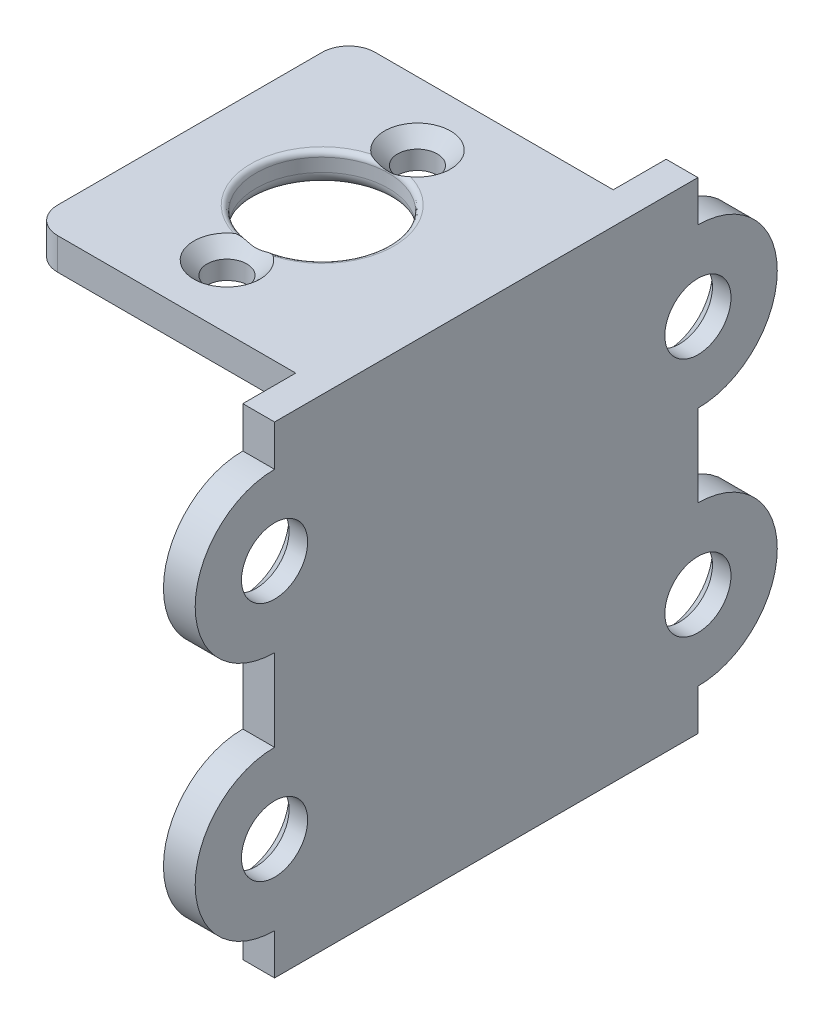
SolidWorks part; units mm, degrees
ref_plane "Front" through (0, 0, 0) normal (0, 0, 1) x (1, 0, 0)
ref_plane "Top" through (0, 0, 0) normal (0, 1, 0) x (1, 0, 0)
ref_plane "Right" through (0, 0, 0) normal (1, 0, 0) x (0, 0, -1)
sketch "Sketch1" plane through (0, 0, 0) normal (0, 1, 0) x (1, 0, 0)
  line L9 (0, 6) -> (5, 6)
  line L11 (-5, -6) -> (5, -6)
  line L12 (-5, -6) -> (-5, 6)
  line L13 (-5, 6) -> (5, 6)
  line L14 (5, -6) -> (5, 6)
  circle A3 centre (0, 0) radius 2.5
  circle A4 centre (0, 3.6) radius 0.75
  circle A5 centre (0, -3.6) radius 0.75
extrude "Boss-Extrude3" add sketch "Sketch1" along normal blind 1.2 contours L11 L14 L9 L13 L12 A5 A4 A3 region at (2.5, 0, -5.8438)
fillet "Fillet10" radius 1 1 edges at (-5, 0.6, 6)
fillet "Fillet11" radius 1 1 edges at (-5, 0.6, -6)
sketch "Sketch5" plane through (5, 0, 0) normal (1, 0, 0) x (0, 0, -1)
  line L4 (6, 1.2) -> (-6, 1.2)
  line L5 (6, 1.2) -> (8, 1.2)
  line L6 (-6, 1.2) -> (-8, 1.2)
  line L11 (-8, -17) -> (8, -17)
  line L12 (-8, 1.2) -> (-8, -0.35)
  line L13 (-8, -6.35) -> (-8, -9.45)
  line L14 (-8, -15.45) -> (-8, -17)
  line L15 (8, -15.45) -> (8, -17)
  line L16 (8, -9.45) -> (8, -6.35)
  line L18 (8, -0.35) -> (8, 1.2)
  arc A0 (8, -6.35) -> (8, -0.35) centre (8, -3.35) ccw
  arc A1 (-8, -0.35) -> (-8, -6.35) centre (-8, -3.35) ccw
  arc A2 (-8, -9.45) -> (-8, -15.45) centre (-8, -12.45) ccw
  arc A3 (8, -9.45) -> (8, -15.45) centre (8, -12.45) cw
extrude "Boss-Extrude5" add sketch "Sketch5" along normal blind 1.2
sketch "Sketch6" plane through (6.2, 0, 0) normal (1, 0, 0) x (0, 0, -1)
  circle A0 centre (8, -3.35) radius 1.25
  circle A1 centre (8, -12.45) radius 1.25
extrude "Cut-Extrude3" cut sketch "Sketch6" against normal blind 1.2
sketch "Sketch7" plane through (5, 0, 0) normal (-1, 0, 0) x (0, 0, 1)
  circle A0 centre (8, -12.45) radius 1.25
  circle A1 centre (8, -3.35) radius 1.25
extrude "Cut-Extrude4" cut sketch "Sketch7" against normal blind 1.2
chamfer "Chamfer5" distance 0.5 angle 45 1 edges at (5, -3.35, 9.25)
chamfer "Chamfer6" distance 0.5 angle 45 3 edges at (5, -12.45, 9.25) (5, -12.45, -9.25) (5, -3.35, -9.25)
fillet "Fillet13" radius 0.5 1 edges at (0, 0, 2.5)
fillet "Fillet14" radius 0.2 1 edges at (0, 1.2, 2.5)
chamfer "Chamfer7" distance 0.5 angle 45 1 edges at (0, 1.2, 4.35)
chamfer "Chamfer8" distance 0.5 angle 45 1 edges at (0, 1.2, -2.85)
